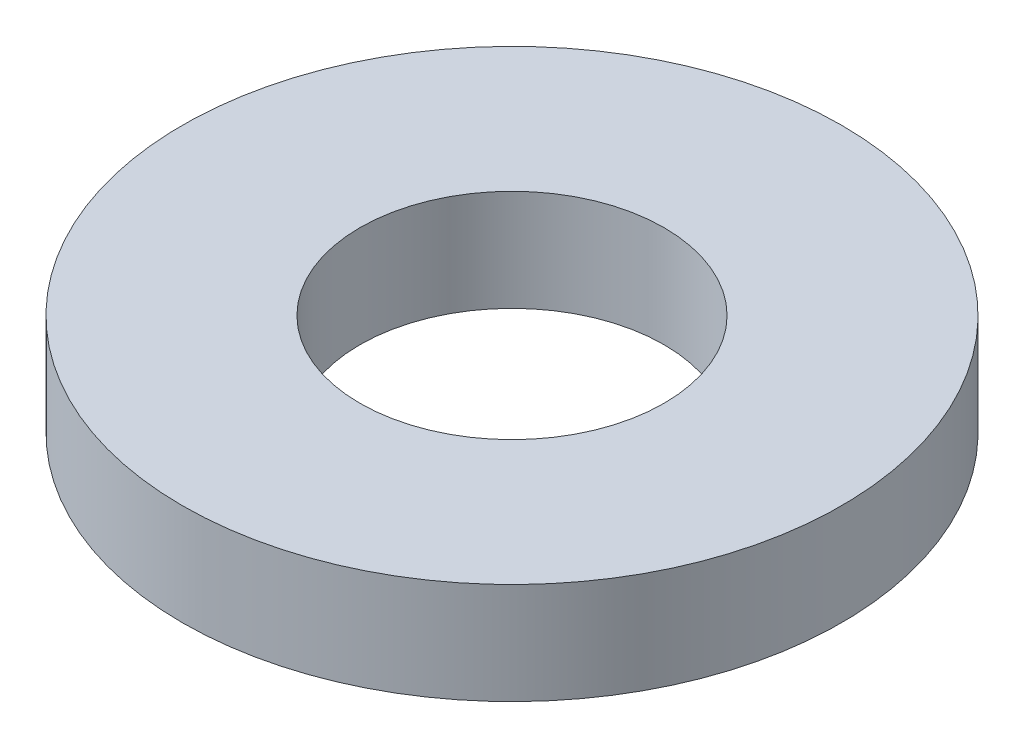
SolidWorks part; units mm, degrees
ref_plane "前视基准面" through (0, 0, 0) normal (0, 0, 1) x (1, 0, 0)
ref_plane "上视基准面" through (0, 0, 0) normal (0, 1, 0) x (1, 0, 0)
ref_plane "右视基准面" through (0, 0, 0) normal (1, 0, 0) x (0, 0, -1)
sketch "草图1" plane through (0, 0, 0) normal (0, 1, 0) x (1, 0, 0)
  circle A0 centre (0, 0) radius 13
extrude "凸台-拉伸1" add sketch "草图1" along normal blind 4
sketch "草图2" plane through (0, 0, 0) normal (0, -1, 0) x (1, 0, 0)
  circle A0 centre (0, 0) radius 6
extrude "切除-拉伸1" cut sketch "草图2" against normal blind 4
